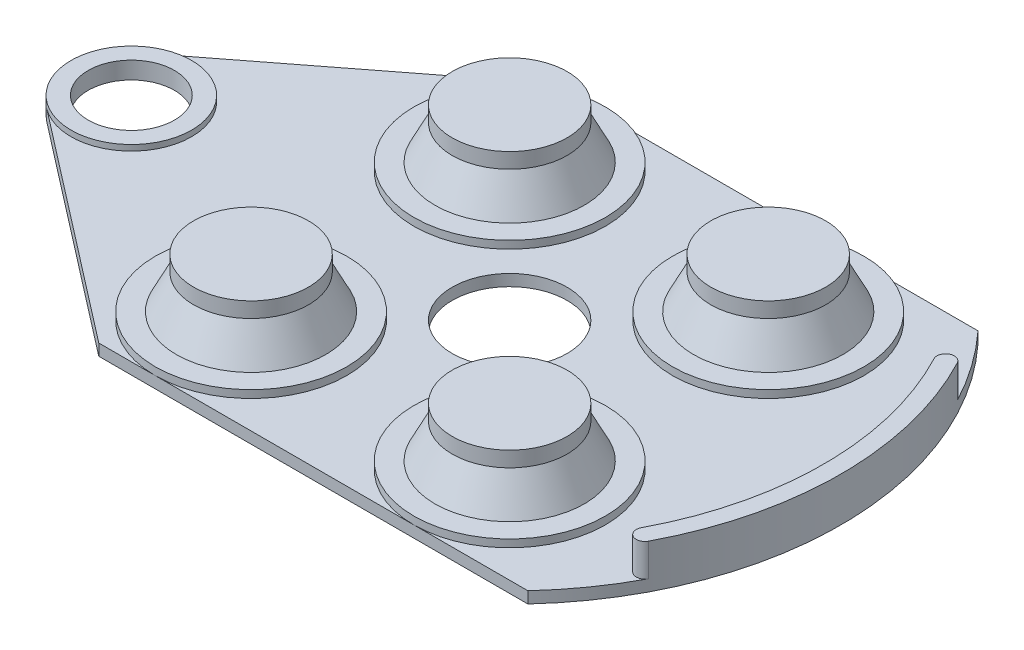
SolidWorks part; units mm, degrees
material "Caoutchouc naturel"
ref_plane "Plan de face" through (0, 0, 0) normal (0, 0, 1) x (1, 0, 0)
ref_plane "Plan de dessus" through (0, 0, 0) normal (0, 1, 0) x (1, 0, 0)
ref_plane "Plan de droite" through (0, 0, 0) normal (1, 0, 0) x (0, 0, -1)
sketch "Esquisse1" plane through (0, 0, 0) normal (0, 1, 0) x (1, 0, 0)
  line L4 (-9.7, 11.75) -> (12.7, 11.75)
  line L5 (-9.7, -11.75) -> (12.7, -11.75)
  line L6 (-9.7, 11.75) -> (-21.6765, 2.4922)
  line L7 (-9.7, -11.75) -> (-21.6765, -2.4922)
  circle A4 centre (0, 0) radius 3
  arc A5 (12.7, 11.75) -> (12.7, -11.75) centre (-0.0068, 0) cw
  arc A6 (-21.6765, -2.4922) -> (-21.6765, 2.4922) centre (-19.75, 0) cw
  circle A7 centre (-19.75, 0) radius 2.25
  circle A8 centre (-19.75, 0) radius 3.15
  arc A9 (14.5124, 7.6404) -> (14.5124, -7.6404) centre (-0.0068, 0) cw
  arc A10 (14.5124, -7.6404) -> (15.3088, -8.0596) centre (14.9106, -7.85) ccw
  arc A11 (14.5124, 7.6404) -> (15.3088, 8.0596) centre (14.9106, 7.85) cw
  arc A12 (15.3088, 8.0596) -> (15.3088, -8.0596) centre (-0.0068, 0) cw
  point P7 (3, 0)
  point P13 (17.3, 0)
  point P14 (-22.9, 0)
  point P18 (16.4, 0)
  point P23 (14.9106, 8.3)
  point P25 (14.9106, -8.3)
  dimension "D3" = 11.75
  dimension "D4" = 22.4
  dimension "D1" = 6
  dimension "D8" = 3.15
  dimension "D9" = 4.5
  dimension "D2" = 23.5
  dimension "D5" = 14.3
  dimension "D6" = 4.6
  dimension "D7" = 40.2
  dimension "D10" = 0.9
  dimension "D11" = 16.6
  dimension "D12" = 0.9
  dimension "D13" = 0.9
extrude "Support" add sketch "Esquisse1" along normal blind 0.6 contours A9 A11 A5 L4 L6 A8 L7 L5 A10 A4 region at (1.5, 0, -11.3026)
extrude "Fixation" add sketch "Esquisse1<4>" along normal blind 0.9 contours A6 A8 A7 region at (-18.4011, 0, -2.7476)
sketch "Esquisse1<4>" plane through (0, 0, 0) normal (0, 1, 0) x (1, 0, 0) same geometry as "Esquisse1"
extrude "Languette" add sketch "Esquisse1<5>" along normal blind 2.3 contours A11 A9 A10 A5 region at (17.1316, 0, 0)
sketch "Esquisse1<5>" plane through (0, 0, 0) normal (0, 1, 0) x (1, 0, 0) same geometry as "Esquisse1"
sketch "Esquisse2" plane through (0, 0.6, 0) normal (0, 1, 0) x (1, 0, 0)
  line L0 (-9.7, -11.75) -> (12.7, -11.75) construction
  line L1 (-9.7, 11.75) -> (12.7, 11.75) construction
  line L2 (-1.75, 6.75) -> (1.75, 6.75)
  line L3 (-6.75, 1.75) -> (-6.75, -1.75)
  line L4 (-1.75, -6.75) -> (1.75, -6.75)
  line L5 (6.75, 1.75) -> (6.75, -1.75)
  circle A0 centre (6.75, 6.75) radius 5
  circle A1 centre (-6.75, 6.75) radius 5
  circle A2 centre (-6.75, -6.75) radius 5
  circle A3 centre (6.75, -6.75) radius 5
  circle A4 centre (-6.75, 6.75) radius 3
  circle A5 centre (6.75, 6.75) radius 3
  circle A6 centre (6.75, -6.75) radius 3
  circle A7 centre (-6.75, -6.75) radius 3
  circle A8 centre (6.75, 6.75) radius 4
  circle A9 centre (-6.75, 6.75) radius 4
  circle A10 centre (-6.75, -6.75) radius 4
  circle A11 centre (6.75, -6.75) radius 4
  point P8 (6.75, 11.75)
  point P9 (-6.75, 11.75)
  point P10 (-6.75, -11.75)
  point P11 (6.75, -11.75)
  point P19 (6.75, 1.75)
  point P21 (6.75, -1.75)
  point P22 (-6.75, -1.75)
  point P23 (-6.75, 1.75)
  point P24 (-1.75, 6.75)
  point P25 (1.75, 6.75)
  point P26 (-1.75, -6.75)
  point P27 (1.75, -6.75)
  point P30 (0, 6.75)
  point P31 (0, 6.75)
  dimension "D1" = 10
  dimension "D2" = 10
  dimension "D3" = 10
  dimension "D4" = 10
  dimension "D5" = 6
  dimension "D6" = 6
  dimension "D7" = 6
  dimension "D8" = 6
  dimension "D10" = 8
  dimension "D11" = 8
  dimension "D12" = 8
  dimension "D13" = 8
  dimension "D9" = 3.5
extrude "Semelle" add sketch "Esquisse2" along normal blind 0.4 contours A1 A9 | A0 A8 | A3 A11 | A2 A10 region at (-3.3145, 0.6, -3.3145) region at (6.75, 0.6, -11.6086) region at (-3.3145, 0.6, 3.3145) region at (10.1855, 0.6, 3.3145)
extrude "Boutons" add sketch "Esquisse2<4>" along normal blind 3 contours A4 | A5 | A6 | A7 region at (-6.75, 0.6, -6.75) region at (6.75, 0.6, -6.75) region at (6.75, 0.6, 6.75) region at (-6.75, 0.6, 6.75)
sketch "Esquisse2<4>" plane through (0, 0.6, 0) normal (0, 1, 0) x (1, 0, 0) same geometry as "Esquisse2"
extrude "Bordure" add sketch "Esquisse2<5>" along normal blind 2.2 contours A9 A4 | A8 A5 | A10 A7 | A11 A6 region at (2.8631, 0.6, -6.75) region at (-10.6369, 0.6, -6.75) region at (-10.6369, 0.6, 6.75) region at (2.8631, 0.6, 6.75)
sketch "Esquisse2<5>" plane through (0, 0.6, 0) normal (0, 1, 0) x (1, 0, 0) same geometry as "Esquisse2"
chamfer "Chanfrein" distance 2 distance2 1 4 edges at (6.75, 2.8, -2.75) (6.75, 2.8, 10.75) (-6.75, 2.8, 10.75) (-6.75, 2.8, -2.75) first distance on face at (6.75, 1, -2.75) first distance on face at (6.75, 1, 10.75) first distance on face at (-6.75, 1, 10.75) first distance on face at (-6.75, 1, -2.75)
sketch "Esquisse3" plane through (0, 0, 0) normal (0, -1, 0) x (1, 0, 0)
  circle A0 centre (6.75, -6.75) radius 2.4
  circle A1 centre (-6.75, -6.75) radius 2.4
  circle A2 centre (6.75, 6.75) radius 2.4
  circle A3 centre (-6.75, 6.75) radius 2.4
  dimension "D1" = 4.8
  dimension "D2" = 4.8
  dimension "D3" = 4.8
  dimension "D4" = 4.8
extrude "Enlèv. mat.-Extru.1" cut sketch "Esquisse3" against normal blind 0.01
